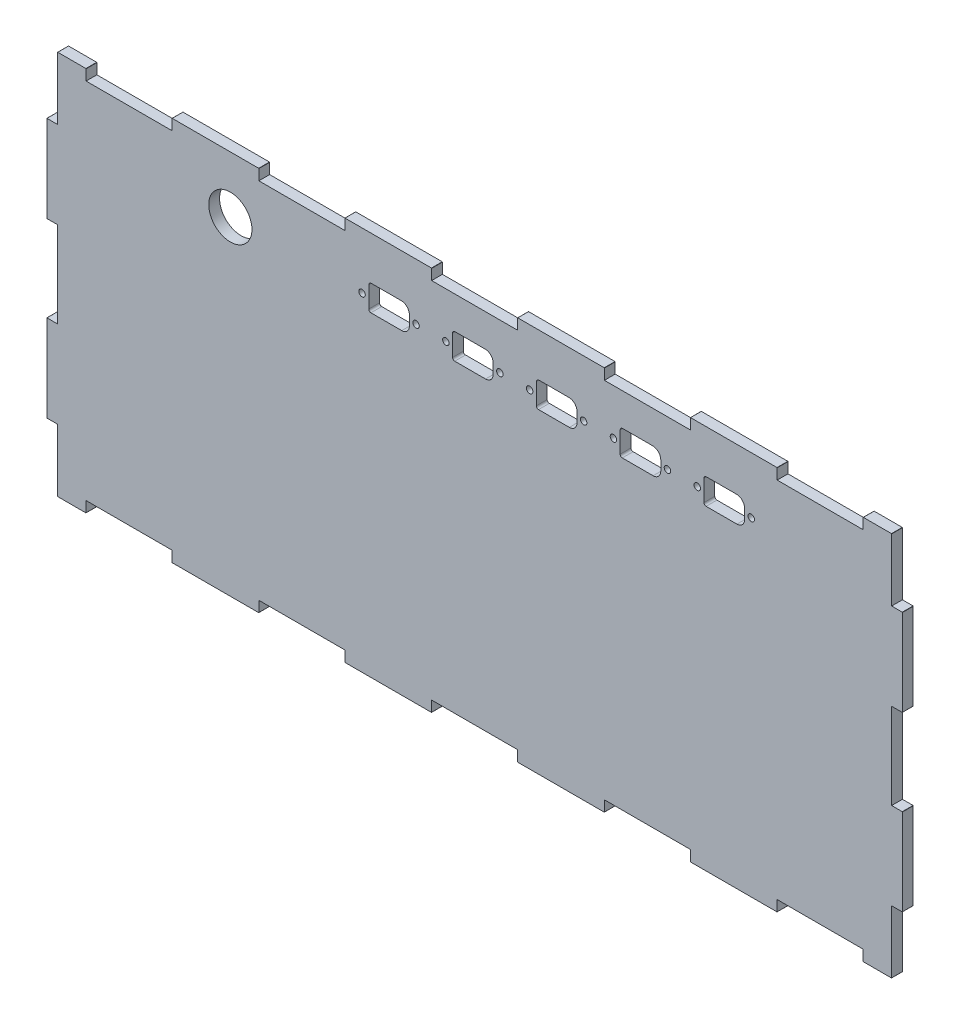
SolidWorks part; units mm, degrees
material "Acrylic (Medium-high impact)"
ref_plane "Front Plane" through (0, 0, 0) normal (0, 0, 1) x (1, 0, 0)
ref_plane "Top Plane" through (0, 0, 0) normal (0, 1, 0) x (1, 0, 0)
ref_plane "Right Plane" through (0, 0, 0) normal (1, 0, 0) x (0, 0, -1)
sketch "Model" plane through (0, 0, 0) normal (0, 0, 1) x (1, 0, 0)
  line L0 (-179.94, -89.08) -> (-179.93, -89.07)
  line L1 (-179.93, -89.07) -> (-179.92, -89.05)
  line L2 (-179.92, -89.05) -> (-179.91, -89.04)
  line L3 (-179.91, -89.04) -> (-179.9, -89.02)
  line L4 (-179.9, -89.02) -> (-179.9, -84.1)
  line L5 (-179.9, -84.1) -> (-140.1, -84.1)
  line L6 (-140.1, -84.1) -> (-140.1, -89.02)
  line L7 (-140.1, -89.02) -> (-140.08, -89.06)
  line L8 (-140.08, -89.06) -> (-140.07, -89.07)
  line L9 (-140.07, -89.07) -> (-140.05, -89.08)
  line L10 (-140.05, -89.08) -> (-140.04, -89.09)
  line L11 (-140.04, -89.09) -> (-140.02, -89.1)
  line L12 (-140.02, -89.1) -> (-99.98, -89.1)
  line L13 (-99.98, -89.1) -> (-99.94, -89.08)
  line L14 (-99.94, -89.08) -> (-99.93, -89.07)
  line L15 (-99.93, -89.07) -> (-99.92, -89.05)
  line L16 (-99.92, -89.05) -> (-99.91, -89.04)
  line L17 (-99.91, -89.04) -> (-99.9, -89.02)
  line L18 (-99.9, -89.02) -> (-99.9, -84.1)
  line L19 (-99.9, -84.1) -> (-60.1, -84.1)
  line L20 (-60.1, -84.1) -> (-60.1, -89.02)
  line L21 (-60.1, -89.02) -> (-60.08, -89.06)
  line L22 (-60.08, -89.06) -> (-60.07, -89.07)
  line L23 (-60.07, -89.07) -> (-60.05, -89.08)
  line L24 (-60.05, -89.08) -> (-60.04, -89.09)
  line L25 (-60.04, -89.09) -> (-60.02, -89.1)
  line L26 (-60.02, -89.1) -> (-19.98, -89.1)
  line L27 (-19.98, -89.1) -> (-19.94, -89.08)
  line L28 (-19.94, -89.08) -> (-19.93, -89.07)
  line L29 (-19.93, -89.07) -> (-19.92, -89.05)
  line L30 (-19.92, -89.05) -> (-19.91, -89.04)
  line L31 (-19.91, -89.04) -> (-19.9, -89.02)
  line L32 (-19.9, -89.02) -> (-19.9, -84.1)
  line L33 (-19.9, -84.1) -> (19.9, -84.1)
  line L34 (19.9, -84.1) -> (19.9, -89.02)
  line L35 (19.9, -89.02) -> (19.92, -89.06)
  line L36 (19.92, -89.06) -> (19.93, -89.07)
  line L37 (19.93, -89.07) -> (19.95, -89.08)
  line L38 (19.95, -89.08) -> (19.96, -89.09)
  line L39 (19.96, -89.09) -> (19.98, -89.1)
  line L40 (19.98, -89.1) -> (60.02, -89.1)
  line L41 (60.02, -89.1) -> (60.06, -89.08)
  line L42 (60.06, -89.08) -> (60.07, -89.07)
  line L43 (60.07, -89.07) -> (60.08, -89.05)
  line L44 (60.08, -89.05) -> (60.09, -89.04)
  line L45 (60.09, -89.04) -> (60.1, -89.02)
  line L46 (60.1, -89.02) -> (60.1, -84.1)
  line L47 (60.1, -84.1) -> (99.9, -84.1)
  line L48 (99.9, -84.1) -> (99.9, -89.02)
  line L49 (99.9, -89.02) -> (99.92, -89.06)
  line L50 (99.92, -89.06) -> (99.93, -89.07)
  line L51 (99.93, -89.07) -> (99.95, -89.08)
  line L52 (99.95, -89.08) -> (99.96, -89.09)
  line L53 (99.96, -89.09) -> (99.98, -89.1)
  line L54 (99.98, -89.1) -> (140.02, -89.1)
  line L55 (140.02, -89.1) -> (140.06, -89.08)
  line L56 (140.06, -89.08) -> (140.07, -89.07)
  line L57 (140.07, -89.07) -> (140.08, -89.05)
  line L58 (140.08, -89.05) -> (140.09, -89.04)
  line L59 (140.09, -89.04) -> (140.1, -89.02)
  line L60 (140.1, -89.02) -> (140.1, -84.1)
  line L61 (140.1, -84.1) -> (179.9, -84.1)
  line L62 (179.9, -84.1) -> (179.9, -89.02)
  line L63 (179.9, -89.02) -> (179.92, -89.06)
  line L64 (179.92, -89.06) -> (179.93, -89.07)
  line L65 (179.93, -89.07) -> (179.95, -89.08)
  line L66 (179.95, -89.08) -> (179.96, -89.09)
  line L67 (179.96, -89.09) -> (179.98, -89.1)
  line L68 (179.98, -89.1) -> (193.02, -89.1)
  line L69 (193.02, -89.1) -> (193.06, -89.08)
  line L70 (193.06, -89.08) -> (193.07, -89.07)
  line L71 (193.07, -89.07) -> (193.08, -89.05)
  line L72 (193.08, -89.05) -> (193.09, -89.04)
  line L73 (193.09, -89.04) -> (193.1, -89.02)
  line L74 (193.1, -89.02) -> (193.1, -60.1)
  line L75 (193.1, -60.1) -> (198.02, -60.1)
  line L76 (198.02, -60.1) -> (198.06, -60.08)
  line L77 (198.06, -60.08) -> (198.07, -60.07)
  line L78 (198.07, -60.07) -> (198.08, -60.05)
  line L79 (198.08, -60.05) -> (198.09, -60.04)
  line L80 (198.09, -60.04) -> (198.1, -60.02)
  line L81 (198.1, -60.02) -> (198.1, -19.98)
  line L82 (198.1, -19.98) -> (198.08, -19.94)
  line L83 (198.08, -19.94) -> (198.07, -19.93)
  line L84 (198.07, -19.93) -> (198.05, -19.92)
  line L85 (198.05, -19.92) -> (198.04, -19.91)
  line L86 (198.04, -19.91) -> (198.02, -19.9)
  line L87 (198.02, -19.9) -> (193.1, -19.9)
  line L88 (193.1, -19.9) -> (193.1, 19.9)
  line L89 (193.1, 19.9) -> (198.02, 19.9)
  line L90 (198.02, 19.9) -> (198.06, 19.92)
  line L91 (198.06, 19.92) -> (198.07, 19.93)
  line L92 (198.07, 19.93) -> (198.08, 19.95)
  line L93 (198.08, 19.95) -> (198.09, 19.96)
  line L94 (198.09, 19.96) -> (198.1, 19.98)
  line L95 (198.1, 19.98) -> (198.1, 60.02)
  line L96 (198.1, 60.02) -> (198.08, 60.06)
  line L97 (198.08, 60.06) -> (198.07, 60.07)
  line L98 (198.07, 60.07) -> (198.05, 60.08)
  line L99 (198.05, 60.08) -> (198.04, 60.09)
  line L100 (198.04, 60.09) -> (198.02, 60.1)
  line L101 (198.02, 60.1) -> (193.1, 60.1)
  line L102 (193.1, 60.1) -> (193.1, 89.02)
  line L103 (193.1, 89.02) -> (193.08, 89.06)
  line L104 (193.08, 89.06) -> (193.07, 89.07)
  line L105 (193.07, 89.07) -> (193.05, 89.08)
  line L106 (193.05, 89.08) -> (193.04, 89.09)
  line L107 (193.04, 89.09) -> (193.02, 89.1)
  line L108 (193.02, 89.1) -> (179.98, 89.1)
  line L109 (179.98, 89.1) -> (179.94, 89.08)
  line L110 (179.94, 89.08) -> (179.93, 89.07)
  line L111 (179.93, 89.07) -> (179.92, 89.05)
  line L112 (179.92, 89.05) -> (179.91, 89.04)
  line L113 (179.91, 89.04) -> (179.9, 89.02)
  line L114 (179.9, 89.02) -> (179.9, 84.1)
  line L115 (179.9, 84.1) -> (140.1, 84.1)
  line L116 (140.1, 84.1) -> (140.1, 89.02)
  line L117 (140.1, 89.02) -> (140.08, 89.06)
  line L118 (140.08, 89.06) -> (140.07, 89.07)
  line L119 (140.07, 89.07) -> (140.05, 89.08)
  line L120 (140.05, 89.08) -> (140.04, 89.09)
  line L121 (140.04, 89.09) -> (140.02, 89.1)
  line L122 (140.02, 89.1) -> (99.98, 89.1)
  line L123 (99.98, 89.1) -> (99.94, 89.08)
  line L124 (99.94, 89.08) -> (99.93, 89.07)
  line L125 (99.93, 89.07) -> (99.92, 89.05)
  line L126 (99.92, 89.05) -> (99.91, 89.04)
  line L127 (99.91, 89.04) -> (99.9, 89.02)
  line L128 (99.9, 89.02) -> (99.9, 84.1)
  line L129 (99.9, 84.1) -> (60.1, 84.1)
  line L130 (60.1, 84.1) -> (60.1, 89.02)
  line L131 (60.1, 89.02) -> (60.08, 89.06)
  line L132 (60.08, 89.06) -> (60.07, 89.07)
  line L133 (60.07, 89.07) -> (60.05, 89.08)
  line L134 (60.05, 89.08) -> (60.04, 89.09)
  line L135 (60.04, 89.09) -> (60.02, 89.1)
  line L136 (60.02, 89.1) -> (19.98, 89.1)
  line L137 (19.98, 89.1) -> (19.94, 89.08)
  line L138 (19.94, 89.08) -> (19.93, 89.07)
  line L139 (19.93, 89.07) -> (19.92, 89.05)
  line L140 (19.92, 89.05) -> (19.91, 89.04)
  line L141 (19.91, 89.04) -> (19.9, 89.02)
  line L142 (19.9, 89.02) -> (19.9, 84.1)
  line L143 (19.9, 84.1) -> (-19.9, 84.1)
  line L144 (-19.9, 84.1) -> (-19.9, 89.02)
  line L145 (-19.9, 89.02) -> (-19.92, 89.06)
  line L146 (-19.92, 89.06) -> (-19.93, 89.07)
  line L147 (-19.93, 89.07) -> (-19.95, 89.08)
  line L148 (-19.95, 89.08) -> (-19.96, 89.09)
  line L149 (-19.96, 89.09) -> (-19.98, 89.1)
  line L150 (-19.98, 89.1) -> (-60.02, 89.1)
  line L151 (-60.02, 89.1) -> (-60.06, 89.08)
  line L152 (-60.06, 89.08) -> (-60.07, 89.07)
  line L153 (-60.07, 89.07) -> (-60.08, 89.05)
  line L154 (-60.08, 89.05) -> (-60.09, 89.04)
  line L155 (-60.09, 89.04) -> (-60.1, 89.02)
  line L156 (-60.1, 89.02) -> (-60.1, 84.1)
  line L157 (-60.1, 84.1) -> (-99.9, 84.1)
  line L158 (-99.9, 84.1) -> (-99.9, 89.02)
  line L159 (-99.9, 89.02) -> (-99.92, 89.06)
  line L160 (-99.92, 89.06) -> (-99.93, 89.07)
  line L161 (-99.93, 89.07) -> (-99.95, 89.08)
  line L162 (-99.95, 89.08) -> (-99.96, 89.09)
  line L163 (-99.96, 89.09) -> (-99.98, 89.1)
  line L164 (-99.98, 89.1) -> (-140.02, 89.1)
  line L165 (-140.02, 89.1) -> (-140.06, 89.08)
  line L166 (-140.06, 89.08) -> (-140.07, 89.07)
  line L167 (-140.07, 89.07) -> (-140.08, 89.05)
  line L168 (-140.08, 89.05) -> (-140.09, 89.04)
  line L169 (-140.09, 89.04) -> (-140.1, 89.02)
  line L170 (-140.1, 89.02) -> (-140.1, 84.1)
  line L171 (-140.1, 84.1) -> (-179.9, 84.1)
  line L172 (-179.9, 84.1) -> (-179.9, 89.02)
  line L173 (-179.9, 89.02) -> (-179.92, 89.06)
  line L174 (-179.92, 89.06) -> (-179.93, 89.07)
  line L175 (-179.93, 89.07) -> (-179.95, 89.08)
  line L176 (-179.95, 89.08) -> (-179.96, 89.09)
  line L177 (-179.96, 89.09) -> (-179.98, 89.1)
  line L178 (-179.98, 89.1) -> (-193.02, 89.1)
  line L179 (-193.02, 89.1) -> (-193.06, 89.08)
  line L180 (-193.06, 89.08) -> (-193.07, 89.07)
  line L181 (-193.07, 89.07) -> (-193.08, 89.05)
  line L182 (-193.08, 89.05) -> (-193.09, 89.04)
  line L183 (-193.09, 89.04) -> (-193.1, 89.02)
  line L184 (-193.1, 89.02) -> (-193.1, 60.1)
  line L185 (-193.1, 60.1) -> (-198.02, 60.1)
  line L186 (-198.02, 60.1) -> (-198.06, 60.08)
  line L187 (-198.06, 60.08) -> (-198.07, 60.07)
  line L188 (-198.07, 60.07) -> (-198.08, 60.05)
  line L189 (-198.08, 60.05) -> (-198.09, 60.04)
  line L190 (-198.09, 60.04) -> (-198.1, 60.02)
  line L191 (-198.1, 60.02) -> (-198.1, 19.98)
  line L192 (-198.1, 19.98) -> (-198.08, 19.94)
  line L193 (-198.08, 19.94) -> (-198.07, 19.93)
  line L194 (-198.07, 19.93) -> (-198.05, 19.92)
  line L195 (-198.05, 19.92) -> (-198.04, 19.91)
  line L196 (-198.04, 19.91) -> (-198.02, 19.9)
  line L197 (-198.02, 19.9) -> (-193.1, 19.9)
  line L198 (-193.1, 19.9) -> (-193.1, -19.9)
  line L199 (-193.1, -19.9) -> (-198.02, -19.9)
  line L200 (-198.02, -19.9) -> (-198.06, -19.92)
  line L201 (-198.06, -19.92) -> (-198.07, -19.93)
  line L202 (-198.07, -19.93) -> (-198.08, -19.95)
  line L203 (-198.08, -19.95) -> (-198.09, -19.96)
  line L204 (-198.09, -19.96) -> (-198.1, -19.98)
  line L205 (-198.1, -19.98) -> (-198.1, -60.02)
  line L206 (-198.1, -60.02) -> (-198.08, -60.06)
  line L207 (-198.08, -60.06) -> (-198.07, -60.07)
  line L208 (-198.07, -60.07) -> (-198.05, -60.08)
  line L209 (-198.05, -60.08) -> (-198.04, -60.09)
  line L210 (-198.04, -60.09) -> (-198.02, -60.1)
  line L211 (-198.02, -60.1) -> (-193.1, -60.1)
  line L212 (-193.1, -60.1) -> (-193.1, -89.02)
  line L213 (-193.1, -89.02) -> (-193.08, -89.06)
  line L214 (-193.08, -89.06) -> (-193.07, -89.07)
  line L215 (-193.07, -89.07) -> (-193.05, -89.08)
  line L216 (-193.05, -89.08) -> (-193.04, -89.09)
  line L217 (-193.04, -89.09) -> (-193.02, -89.1)
  line L218 (-193.02, -89.1) -> (-179.98, -89.1)
  line L219 (-179.98, -89.1) -> (-179.94, -89.08)
extrude "Boss-Extrude1" add sketch "Model" along normal blind 5
sketch "Sketch2" plane through (0, 0, 5) normal (0, 0, 1) x (1, 0, 0)
  line L5 (-30.2088, 62.97) -> (-10.2088, 62.97) construction
  line L13 (-33.7338, 57.12) -> (-48.0088, 57.12)
  line L14 (-47.8088, 69.02) -> (-33.9338, 69.02)
  line L15 (-49.0088, 58.12) -> (-49.0088, 67.82)
  line L16 (-30.2088, 60.645) -> (-30.2088, 65.295)
  line L17 (5.0662, 57.12) -> (-9.2088, 57.12)
  line L18 (-9.0088, 69.02) -> (4.8662, 69.02)
  line L19 (-10.2088, 58.12) -> (-10.2088, 67.82)
  line L20 (8.5912, 60.645) -> (8.5912, 65.295)
  line L21 (43.8662, 57.12) -> (29.5912, 57.12)
  line L22 (29.7912, 69.02) -> (43.6662, 69.02)
  line L23 (28.5912, 58.12) -> (28.5912, 67.82)
  line L24 (47.3912, 60.645) -> (47.3912, 65.295)
  line L25 (82.6662, 57.12) -> (68.3912, 57.12)
  line L26 (68.5912, 69.02) -> (82.4662, 69.02)
  line L27 (67.3912, 58.12) -> (67.3912, 67.82)
  line L28 (86.1912, 60.645) -> (86.1912, 65.295)
  line L37 (8.5912, 62.97) -> (28.5912, 62.97) construction
  line L38 (47.3912, 62.97) -> (67.3912, 62.97) construction
  line L39 (121.4662, 57.12) -> (107.1912, 57.12)
  line L40 (107.3912, 69.02) -> (121.2662, 69.02)
  line L45 (106.1912, 58.12) -> (106.1912, 67.82)
  line L46 (124.9912, 60.645) -> (124.9912, 65.295)
  line L47 (86.1912, 62.97) -> (106.1912, 62.97) construction
  line L48 (-52.1088, 62.97) -> (-49.0088, 62.97) construction
  line L49 (-13.3088, 62.97) -> (-10.2088, 62.97) construction
  line L50 (25.4912, 62.97) -> (28.5912, 62.97) construction
  line L51 (64.2912, 62.97) -> (67.3912, 62.97) construction
  line L52 (103.0912, 62.97) -> (106.1912, 62.97) construction
  line L53 (128.0912, 62.97) -> (193.1, 62.97) construction
  line L54 (193.1, 60.1) -> (193.1, 89.02) construction
  line L55 (193.1, 62.97) -> (193.1, 89.02) construction
  arc A12 (-30.2088, 60.645) -> (-33.7338, 57.12) centre (-33.7338, 60.645) cw
  arc A13 (-30.2088, 65.295) -> (-33.9338, 69.02) centre (-33.9338, 65.295) ccw
  arc A14 (-48.0088, 57.12) -> (-49.0088, 58.12) centre (-48.0088, 58.12) cw
  arc A15 (-49.0088, 67.82) -> (-47.8088, 69.02) centre (-47.8088, 67.82) cw
  arc A16 (8.5912, 60.645) -> (5.0662, 57.12) centre (5.0662, 60.645) cw
  arc A17 (8.5912, 65.295) -> (4.8662, 69.02) centre (4.8662, 65.295) ccw
  arc A18 (-9.2088, 57.12) -> (-10.2088, 58.12) centre (-9.2088, 58.12) cw
  arc A19 (-10.2088, 67.82) -> (-9.0088, 69.02) centre (-9.0088, 67.82) cw
  arc A20 (47.3912, 60.645) -> (43.8662, 57.12) centre (43.8662, 60.645) cw
  arc A21 (47.3912, 65.295) -> (43.6662, 69.02) centre (43.6662, 65.295) ccw
  arc A22 (29.5912, 57.12) -> (28.5912, 58.12) centre (29.5912, 58.12) cw
  arc A23 (28.5912, 67.82) -> (29.7912, 69.02) centre (29.7912, 67.82) cw
  arc A24 (86.1912, 60.645) -> (82.6662, 57.12) centre (82.6662, 60.645) cw
  arc A25 (86.1912, 65.295) -> (82.4662, 69.02) centre (82.4662, 65.295) ccw
  arc A26 (68.3912, 57.12) -> (67.3912, 58.12) centre (68.3912, 58.12) cw
  arc A27 (67.3912, 67.82) -> (68.5912, 69.02) centre (68.5912, 67.82) cw
  arc A40 (124.9912, 60.645) -> (121.4662, 57.12) centre (121.4662, 60.645) cw
  arc A41 (124.9912, 65.295) -> (121.2662, 69.02) centre (121.2662, 65.295) ccw
  arc A42 (107.1912, 57.12) -> (106.1912, 58.12) centre (107.1912, 58.12) cw
  arc A43 (106.1912, 67.82) -> (107.3912, 69.02) centre (107.3912, 67.82) cw
  circle A44 centre (-52.1088, 62.97) radius 1.5
  circle A45 centre (-27.1088, 62.97) radius 1.5
  circle A46 centre (-13.3088, 62.97) radius 1.5
  circle A47 centre (11.6912, 62.97) radius 1.5
  circle A48 centre (25.4912, 62.97) radius 1.5
  circle A49 centre (50.4912, 62.97) radius 1.5
  circle A50 centre (64.2912, 62.97) radius 1.5
  circle A51 centre (89.2912, 62.97) radius 1.5
  circle A52 centre (103.0912, 62.97) radius 1.5
  circle A53 centre (128.0912, 62.97) radius 1.5
  dimension "D7" = 3
  dimension "D9" = 3
  dimension "D1" = 20
  dimension "D2" = 20
  dimension "D3" = 20
  dimension "D4" = 20
  dimension "D5" = 25
extrude "Cut-Extrude1" cut sketch "Sketch2" against normal through all
sketch "Sketch3" plane through (0, 0, 5) normal (0, 0, 1) x (1, 0, 0)
  line L1 (-53.6088, 62.97) -> (-113.1, 62.97) construction
  circle A0 centre (-113.1, 62.97) radius 10
  circle A1 centre (-52.1088, 62.97) radius 1.5 construction
  dimension "D1" = 20
extrude "Cut-Extrude2" cut sketch "Sketch3" against normal through all
